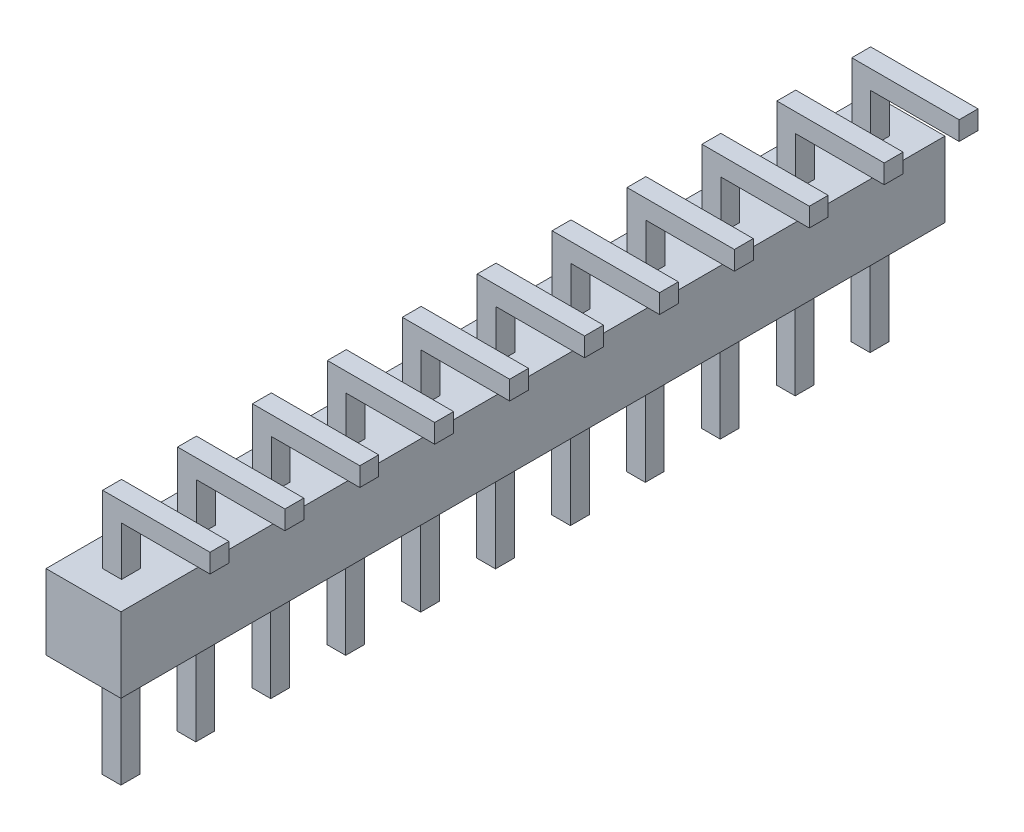
SolidWorks part; units mm, degrees
ref_plane "Front Plane" through (0, 0, 0) normal (0, 0, 1) x (1, 0, 0)
ref_plane "Top Plane" through (0, 0, 0) normal (0, 1, 0) x (1, 0, 0)
ref_plane "Right Plane" through (0, 0, 0) normal (1, 0, 0) x (0, 0, -1)
sketch "Sketch1" plane through (0, 0, 0) normal (0, 0, 1) x (1, 0, 0)
  line L1 (0, 0) -> (2.54, 0)
  line L2 (0, 0) -> (0, 2.54)
  line L3 (0, 2.54) -> (2.54, 2.54)
  line L4 (2.54, 0) -> (2.54, 2.54)
  dimension "D1" = 2.54
  dimension "D2" = 2.54
extrude "Boss-Extrude1" add sketch "Sketch1" along normal blind 27.94
sketch "Sketch2" plane through (0, 0, 0) normal (0, -1, 0) x (1, 0, 0)
  line L0 (0, 27.94) -> (2.54, 27.94) construction
  line L1 (0.95, 26.99) -> (1.59, 26.99)
  line L2 (0.95, 26.99) -> (0.95, 26.35)
  line L3 (0.95, 26.35) -> (1.59, 26.35)
  line L4 (1.59, 26.99) -> (1.59, 26.35)
  line L5 (0, 27.94) -> (0, 0) construction
  dimension "D1" = 0.64
  dimension "D2" = 0.64
  dimension "D3" = 0.95
  dimension "D4" = 0.95
extrude "Boss-Extrude2" add sketch "Sketch2" along normal blind 3.5
pattern_linear "LPattern1" count 11 spacing 2.54 along (0, 0, -1) of "Boss-Extrude2"
sketch "Sketch3" plane through (0, 2.54, 0) normal (0, 1, 0) x (1, 0, 0)
  line L0 (2.54, 0) -> (0, 0) construction
  line L1 (0.96, -1.58) -> (1.6, -1.58)
  line L2 (0.96, -1.58) -> (0.96, -0.94)
  line L3 (0.96, -0.94) -> (1.6, -0.94)
  line L4 (1.6, -1.58) -> (1.6, -0.94)
  line L5 (2.54, -27.94) -> (2.54, 0) construction
  dimension "D1" = 0.64
  dimension "D2" = 0.64
  dimension "D3" = 0.94
  dimension "D4" = 0.94
extrude "Boss-Extrude3" add sketch "Sketch3" along normal blind 2.3
pattern_linear "LPattern2" count 11 spacing 2.54 along (0, 0, 1) of "Boss-Extrude3"
sketch "Sketch4" plane through (1.6, 0, 0) normal (1, 0, 0) x (0, 0, -1)
  line L0 (-1.58, 4.84) -> (-1.58, 2.54) construction
  line L1 (-0.94, 4.84) -> (-1.58, 4.84)
  line L2 (-0.94, 4.84) -> (-0.94, 4.2)
  line L3 (-0.94, 4.2) -> (-1.58, 4.2)
  line L4 (-1.58, 4.84) -> (-1.58, 4.2)
  dimension "D1" = 0.64
extrude "Boss-Extrude4" add sketch "Sketch4" along normal blind 3
pattern_linear "LPattern3" count 11 spacing 2.54 along (0, 0, 1) of "Boss-Extrude4"
